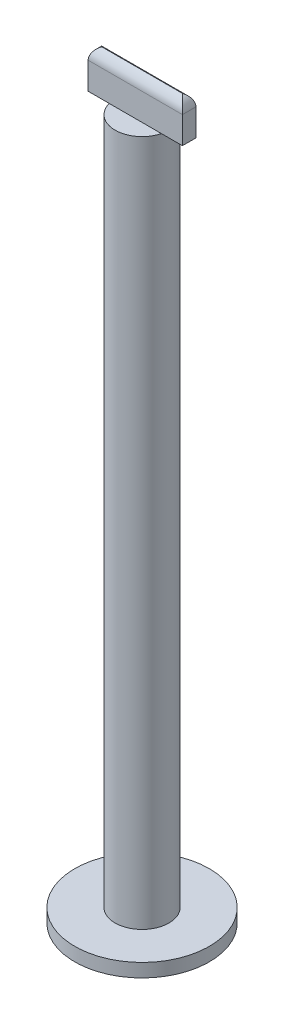
SolidWorks part; units mm, degrees
ref_plane "Front Plane" through (0, 0, 0) normal (0, 0, 1) x (1, 0, 0)
ref_plane "Top Plane" through (0, 0, 0) normal (0, 1, 0) x (1, 0, 0)
ref_plane "Right Plane" through (0, 0, 0) normal (1, 0, 0) x (0, 0, -1)
sketch "Sketch1" plane through (0, 0, 0) normal (0, 1, 0) x (1, 0, 0)
  circle A0 centre (0, 0) radius 2
extrude "Boss-Extrude1" add sketch "Sketch1" along normal blind 52
sketch "Sketch2" plane through (0, 0, 0) normal (0, -1, 0) x (1, 0, 0)
  circle A0 centre (0, 0) radius 5
extrude "Boss-Extrude2" add sketch "Sketch2" against normal blind 1
sketch "Sketch3" plane through (0, 52, 0) normal (0, 1, 0) x (1, 0, 0)
  line L1 (-3.5, -0.5) -> (3.5, -0.5)
  line L2 (-3.5, -0.5) -> (-3.5, 0.5)
  line L3 (-3.5, 0.5) -> (3.5, 0.5)
  line L4 (3.5, -0.5) -> (3.5, 0.5)
  line L5 (-3.5, -0.5) -> (3.5, 0.5) construction
  line L6 (-3.5, 0.5) -> (3.5, -0.5) construction
  point P0 (0, 0)
  dimension "D1" = 1
  dimension "D2" = 7
extrude "Boss-Extrude3" add sketch "Sketch3" along normal blind 3
fillet "Fillet1" radius 1 4 edges at (0, 55, 0.5) (-3.5, 55, 0) (0, 55, -0.5) (3.5, 55, 0)
